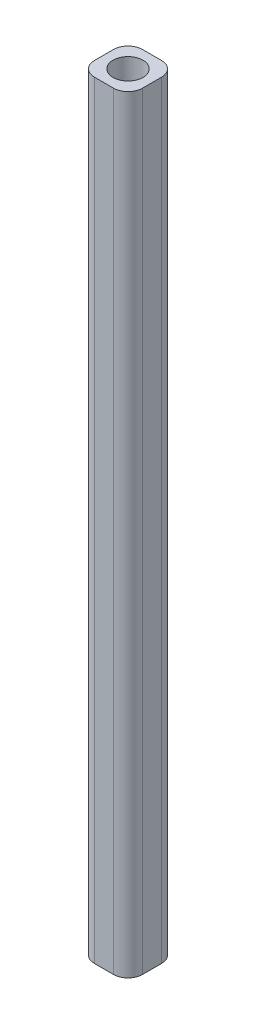
SolidWorks part; units mm, degrees
note: The reader was unsure of these and kept them because the rebuilt part matched: shared geometry of "Sketch2<2>".
ref_plane "Front Plane" through (0, 0, 0) normal (0, 0, 1) x (1, 0, 0)
ref_plane "Top Plane" through (0, 0, 0) normal (0, 1, 0) x (1, 0, 0)
ref_plane "Right Plane" through (0, 0, 0) normal (1, 0, 0) x (0, 0, -1)
sketch "Sketch1" plane through (0, 0, 0) normal (0, 1, 0) x (1, 0, 0)
  line L1 (-5, 5) -> (5, 5)
  line L2 (-5, 5) -> (-5, -5)
  line L3 (-5, -5) -> (5, -5)
  line L4 (5, 5) -> (5, -5)
  line L5 (-5, 5) -> (5, -5) construction
  line L6 (-5, -5) -> (5, 5) construction
  point P0 (0, 0)
  dimension "D1" = 10
  dimension "D2" = 10
extrude "Boss-Extrude1" add sketch "Sketch1" along normal blind 160
fillet "Fillet1" radius 3
sketch "Sketch2" plane through (0, 160, 0) normal (0, 1, 0) x (1, 0, 0)
  circle A0 centre (0, 0) radius 3.125
  dimension "D1" = 6.25
extrude "Cut-Extrude1" cut sketch "Sketch2" against normal blind 4.7
extrude "Cut-Extrude2" cut sketch "Sketch2<2>" along normal blind 4.7 from surface
sketch "Sketch2<2>" plane through (0, 160, 0) normal (0, 1, 0) x (1, 0, 0) same geometry as "Sketch2"
